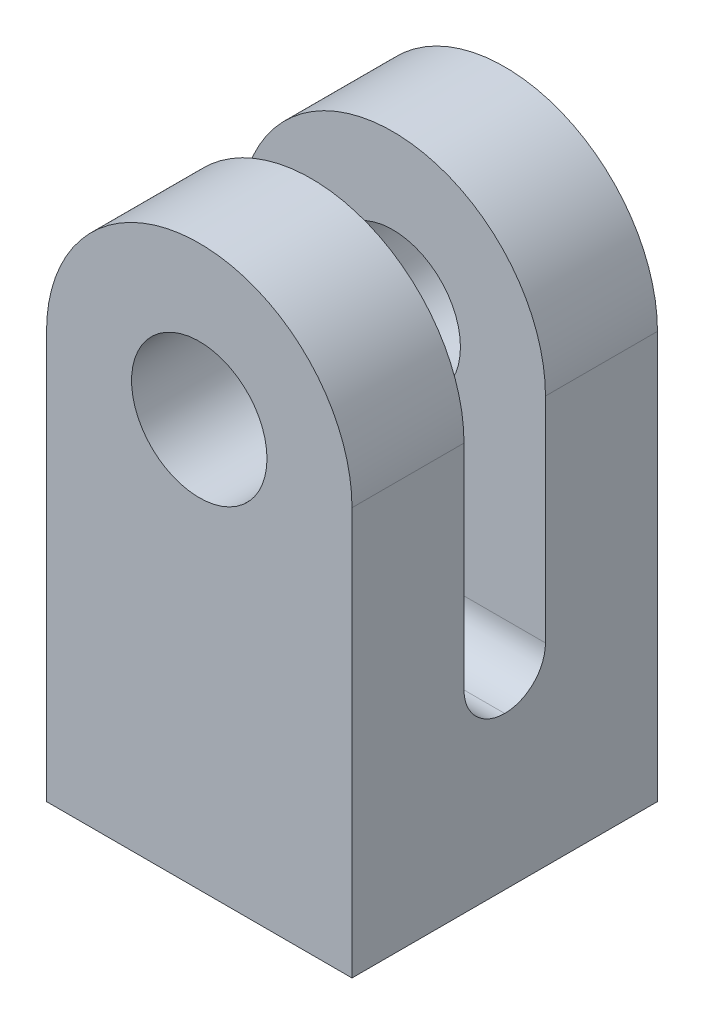
SolidWorks part; units mm, degrees
ref_plane "Front Plane" through (0, 0, 0) normal (0, 0, 1) x (1, 0, 0)
ref_plane "Top Plane" through (0, 0, 0) normal (0, 1, 0) x (1, 0, 0)
ref_plane "Right Plane" through (0, 0, 0) normal (1, 0, 0) x (0, 0, -1)
sketch "Sketch1" plane through (0, 0, 0) normal (0, 0, 1) x (1, 0, 0)
  line L1 (0, 0) -> (30, 0)
  line L2 (0, 0) -> (0, 40)
  line L4 (30, 0) -> (30, 40)
  arc A0 (30, 40) -> (0, 40) centre (15, 40) ccw
  circle A1 centre (15, 40) radius 6.65
  dimension "D1" = 30
  dimension "D2" = 40
  dimension "D3" = 13.3
extrude "Boss-Extrude1" add sketch "Sketch1" along normal blind 30
sketch "Sketch2" plane through (0, 0, 0) normal (-1, 0, 0) x (0, 0, 1)
  line L0 (30, 0) -> (0, 0) construction
  line L1 (11, 15) -> (19, 15)
  line L2 (11, 15) -> (11, 55)
  line L3 (11, 55) -> (19, 55)
  line L4 (19, 15) -> (19, 55)
  line L5 (30, 55) -> (0, 55) construction
  point P8 (15, 55)
  point P9 (15, 0)
  dimension "D1" = 8
  dimension "D2" = 40
extrude "Cut-Extrude1" cut sketch "Sketch2" against normal through all contours L3 L4 L1 L2
fillet "Fillet1" radius 4 2 edges at (15, 15, 19) (15, 15, 11)
